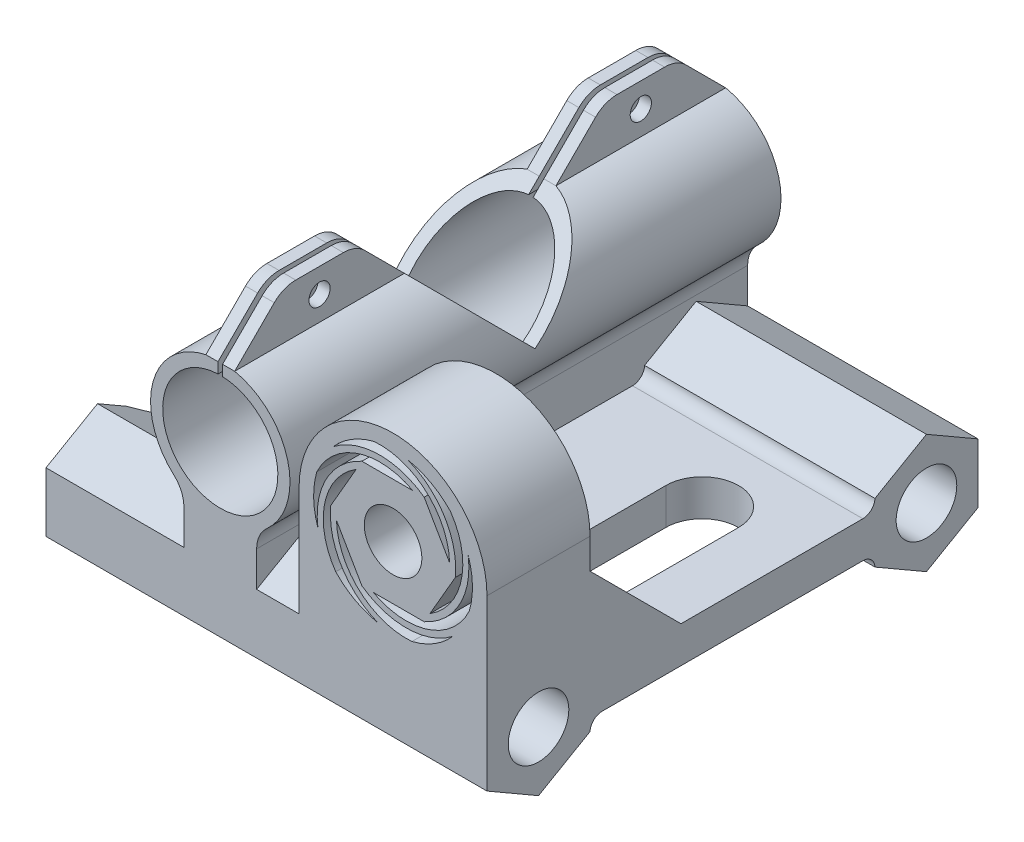
SolidWorks part; units mm, degrees
ref_plane "Front Plane" through (0, 0, 0) normal (0, 0, 1) x (1, 0, 0)
ref_plane "Top Plane" through (0, 0, 0) normal (0, 1, 0) x (1, 0, 0)
ref_plane "Right Plane" through (0, 0, 0) normal (1, 0, 0) x (0, 0, -1)
sketch "Sketch2" plane through (0, 0, 0) normal (1, 0, 0) x (0, 0, -1)
  line L0 (-5.6113, 0) -> (58.3887, 0) construction
  line L1 (2.8887, 3) -> (49.8887, 3)
  line L2 (66.8887, 4.9075) -> (58.3887, 9.815)
  line L3 (58.3887, 9.815) -> (49.8887, 4.9075)
  line L4 (49.8887, 4.9075) -> (49.8887, 3)
  line L5 (49.8887, -4.9075) -> (58.3887, -9.815)
  line L6 (58.3887, -9.815) -> (66.8887, -4.9075)
  line L7 (66.8887, -4.9075) -> (66.8887, 4.9075)
  line L8 (2.8887, 4.9075) -> (-5.6113, 9.815)
  line L9 (-5.6113, 9.815) -> (-14.1113, 4.9075)
  line L10 (-14.1113, 4.9075) -> (-14.1113, -4.9075)
  line L11 (-14.1113, -4.9075) -> (-5.6113, -9.815)
  line L12 (-5.6113, -9.815) -> (2.8887, -4.9075)
  line L13 (2.8887, -4.9075) -> (2.8887, -3)
  line L14 (2.8887, -3) -> (49.8887, -3)
  line L15 (49.8887, -3) -> (49.8887, -4.9075)
  line L16 (2.8887, 3) -> (2.8887, 4.9075)
  circle A2 centre (58.3887, 0) radius 8.5 construction
  circle A3 centre (-5.6113, 0) radius 8.5 construction
  dimension "D2" = 17
  dimension "D3" = 47
  dimension "D4" = 6
  dimension "D5" = 3
extrude "Boss-Extrude1" add sketch "Sketch2" along normal blind 72.75
sketch "Sketch3" plane through (0, 3, 0) normal (0, 1, 0) x (1, 0, 0)
  line L0 (0, 49.8887) -> (47, 2.8887) construction
  line L1 (72.75, 2.8887) -> (0, 2.8887) construction
  line L2 (0, 2.8887) -> (47, 49.8887) construction
  line L3 (72.75, 49.8887) -> (0, 49.8887) construction
  line L4 (72.75, 2.8887) -> (0, 2.8887) construction
  line L5 (1.75, 48.1387) -> (1.75, 2.8887)
  line L6 (39, 41.8887) -> (8, 41.8887) construction
  line L7 (39, 41.8887) -> (39, 10.8887) construction
  line L8 (39, 10.8887) -> (8, 10.8887) construction
  line L9 (8, 41.8887) -> (8, 10.8887) construction
  line L10 (1.75, 48.1387) -> (45.25, 48.1387) construction
  line L11 (45.25, 48.1387) -> (45.25, 4.6387) construction
  line L12 (45.25, 4.6387) -> (1.75, 4.6387) construction
  line L13 (1.75, 2.8887) -> (0, -0.8613)
  line L14 (0, 2.8887) -> (0, -5.6113) construction
  line L16 (1.75, 48.1387) -> (1.75, 49.8887)
  line L18 (1.75, 49.8887) -> (0, 51.6387)
  line L20 (0, 58.3887) -> (0, 49.8887) construction
  line L21 (0, 51.6387) -> (0, -0.8613)
  dimension "D1" = 45
  dimension "D2" = 45
  dimension "D3" = 31
  dimension "D6" = 43.5
extrude "Cut-Extrude1" cut sketch "Sketch3" against normal blind 28 and the other way blind 30
fillet "Fillet3" radius 2 4 edges at (37.25, -3, -2.8887) (37.25, -3, -49.8887) (37.25, 3, -49.8887) (37.25, 3, -2.8887)
sketch "Sketch4" plane through (0, 0, -66.8887) normal (0, 0, -1) x (-1, 0, 0)
  line L0 (-28.75, 3) -> (-28.75, 23) construction
  line L1 (-72.75, 3) -> (-1.75, 3) construction
  line L3 (-34.75, 3) -> (-34.75, 13.1893)
  line L4 (-22.75, 3) -> (-22.75, 13.1893)
  line L5 (-22.75, 3) -> (-34.75, 3)
  line L6 (-26.375, 34.2521) -> (-26.375, 42.2521)
  line L7 (-26.375, 42.2521) -> (-28.375, 42.2521)
  line L8 (-28.375, 42.2521) -> (-28.375, 32.4926)
  line L9 (-31.125, 34.2521) -> (-31.125, 42.2521)
  line L10 (-31.125, 42.2521) -> (-29.125, 42.2521)
  line L11 (-29.125, 42.2521) -> (-29.125, 32.4926)
  line L12 (-1.75, 4.9075) -> (-1.75, -4.9075) construction
  arc A0 (-29.125, 32.4926) -> (-28.375, 32.4926) centre (-28.75, 23) ccw
  arc A1 (-22.75, 13.1893) -> (-26.375, 34.2521) centre (-28.75, 23) ccw
  arc A3 (-31.125, 34.2521) -> (-34.75, 13.1893) centre (-28.75, 23) ccw
  dimension "D1" = 2
  dimension "D2" = 2
  dimension "D3" = 0.75
  dimension "D10" = 8
  dimension "D6" = 19
  dimension "D7" = 23
  dimension "D4" = 12
  dimension "D5" = 6
  dimension "D8" = 20
  dimension "D9" = 0.375
  dimension "D11" = 27
extrude "Boss-Extrude2" add sketch "Sketch4" against normal up to surface (81 mm away) up to face at (36.375, 0, 14.1113)
fillet "Fillet4" radius 5 2 edges at (22.75, 13.1893, -26.3887) (34.75, 13.1893, -26.3887)
sketch "Sketch5" plane through (0, 0, 14.1113) normal (0, 0, -1) x (-1, 0, 0)
  line L0 (-28.75, 23) -> (-110, 23) construction
  line L1 (-72.75, 23) -> (-72.75, 4.9075)
  line L2 (-72.75, 4.9075) -> (-34.75, 4.9075) construction
  line L3 (-72.75, 4.9075) -> (-41.75, 4.9075)
  line L4 (-41.75, 4.9075) -> (-41.75, 23)
  circle A0 centre (-57.25, 23) radius 4.75
  arc A1 (-41.75, 23) -> (-72.75, 23) centre (-57.25, 23) ccw
  arc A2 (-29.125, 32.4926) -> (-28.375, 32.4926) centre (-28.75, 23) ccw construction
  dimension "D1" = 9.5
  dimension "D3" = 31
  dimension "D4" = 0
  dimension "D5" = 28.5
  dimension "D2" = 28.5
extrude "Boss-Extrude7" add sketch "Sketch5" along normal up to vertex (17 mm away) up to point (72.75, 4.9075, -2.8887)
sketch "Sketch6" plane through (0, 0, -2.8887) normal (0, 0, -1) x (-1, 0, 0)
  line L0 (-41.75, 9.815) -> (-34.75, 9.815) construction
  line L1 (-49.7444, 23) -> (-53.4972, 29.5)
  line L2 (-53.4972, 29.5) -> (-61.0028, 29.5)
  line L3 (-61.0028, 29.5) -> (-64.7556, 23)
  line L4 (-64.7556, 23) -> (-61.0028, 16.5)
  line L5 (-61.0028, 16.5) -> (-53.4972, 16.5)
  line L6 (-53.4972, 16.5) -> (-49.7444, 23)
  circle A0 centre (-57.25, 23) radius 6.5 construction
  dimension "D1" = 13
extrude "Cut-Extrude2" cut sketch "Sketch6" against normal blind 7.5
sketch "Sketch7" plane through (0, 0, 0) normal (-1, 0, 0) x (0, 0, 1)
  line L0 (14.1113, 42.2521) -> (-66.8887, 42.2521) construction
  line L1 (-66.8887, 34.2521) -> (-38.8887, 34.2521) construction
  line L2 (-66.8887, 34.2521) -> (-66.8887, 14.4284) construction
  line L3 (-66.8887, 14.4284) -> (-38.8887, 14.4284) construction
  line L4 (-38.8887, 34.2521) -> (-38.8887, 14.4284) construction
  line L6 (14.1113, 14.4284) -> (-13.8887, 14.4284) construction
  line L7 (14.1113, 14.4284) -> (14.1113, 34.2521) construction
  line L8 (14.1113, 34.2521) -> (-13.8887, 34.2521) construction
  line L9 (-13.8887, 14.4284) -> (-13.8887, 34.2521) construction
  line L10 (14.1113, 38.2521) -> (-67.3887, 38.2521) construction
  line L11 (14.1113, 14.4284) -> (14.1113, 34.2521) construction
  line L12 (-38.8887, 42.2521) -> (-66.8887, 42.2521) construction
  line L13 (-52.8887, 34.2521) -> (-52.8887, 42.2521) construction
  line L15 (0.1113, 34.2521) -> (0.1113, 42.2521) construction
  line L16 (-38.8887, 34.2521) -> (-26.3887, 21.7521)
  line L17 (-13.8887, 34.2521) -> (-26.3887, 21.7521)
  line L18 (-13.8887, 34.2521) -> (-13.8887, 42.2521)
  line L19 (-38.8887, 34.2521) -> (-38.8887, 42.2521)
  line L20 (-38.8887, 42.2521) -> (-13.8887, 42.2521)
  line L21 (-66.8887, 14.4284) -> (14.1113, 14.4284) construction
  line L22 (-13.8887, 42.2521) -> (14.1113, 42.2521) construction
  line L25 (14.1113, 42.2521) -> (14.1113, 34.2521) construction
  line L26 (14.1113, 34.2521) -> (-66.8887, 34.2521) construction
  circle A0 centre (0.1113, 38.2521) radius 1.75
  circle A1 centre (-52.8887, 38.2521) radius 1.75
  dimension "D3" = 3.5
  dimension "D1" = 28
  dimension "D2" = 28
  dimension "D4" = 45
  dimension "D5" = 45
extrude "Cut-Extrude3" cut sketch "Sketch7" against normal up to surface (41.75 mm away) up to face at (41.75, 13.126, 5.6113)
chamfer "Chamfer1" distance 8 angle 45 8 edges at (27.375, 42.2521, -66.8887) (30.125, 42.2521, -66.8887) (30.125, 42.2521, -38.8887) (27.375, 42.2521, -38.8887) (30.125, 42.2521, 14.1113) (27.375, 42.2521, 14.1113) (27.375, 42.2521, -13.8887) (30.125, 42.2521, -13.8887)
fillet "Fillet5" radius 5 8 edges at (27.375, 42.2521, 6.1113) (30.125, 42.2521, 6.1113) (30.125, 42.2521, -5.8887) (27.375, 42.2521, -5.8887) (27.375, 42.2521, -46.8887) (30.125, 42.2521, -46.8887) (30.125, 42.2521, -58.8887) (27.375, 42.2521, -58.8887)
sketch "Sketch9" plane through (72.75, 0, 0) normal (1, 0, 0) x (0, 0, -1)
  line L0 (-9.8613, 7.3612) -> (-1.3613, -7.3612) construction
  line L1 (-5.6113, 9.815) -> (-14.1113, 4.9075) construction
  line L2 (-5.6113, -9.815) -> (2.8887, -4.9075) construction
  line L3 (54.1387, -7.3612) -> (62.6387, 7.3612) construction
  line L4 (49.8887, -4.9075) -> (58.3887, -9.815) construction
  circle A0 centre (58.3887, 0) radius 5
  circle A1 centre (-5.6113, 0) radius 5
  dimension "D1" = 10
extrude "Cut-Extrude5" cut sketch "Sketch9" against normal up to surface (50 mm away) up to face at (22.75, 6.5862, -26.3887)
sketch "Sketch14" plane through (0, 3, 0) normal (0, 1, 0) x (1, 0, 0)
  line L0 (57.75, 64.8887) -> (57.75, -14.1113) construction
  line L3 (72.75, 47.8909) -> (72.75, 4.8866) construction
  line L4 (57.75, 36.3887) -> (57.75, 14.3887) construction
  line L5 (63.75, 36.3887) -> (63.75, 14.3887)
  line L6 (51.75, 36.3887) -> (51.75, 14.3887)
  line L8 (41.75, -14.1113) -> (34.75, -14.1113) construction
  arc A0 (63.75, 36.3887) -> (51.75, 36.3887) centre (57.75, 36.3887) ccw
  arc A1 (51.75, 14.3887) -> (63.75, 14.3887) centre (57.75, 14.3887) ccw
  point P10 (57.75, 25.3887)
  dimension "D2" = 6
  dimension "D1" = 15
  dimension "D3" = 22
extrude "Cut-Extrude8" cut sketch "Sketch14" against normal blind 10
sketch "Sketch18" plane through (72.75, 0, 0) normal (1, 0, 0) x (0, 0, -1)
  line L0 (2.8941, 18) -> (2.8941, 3)
  line L1 (2.8941, 3) -> (17.8941, 3)
  line L2 (47.8909, 3) -> (4.8866, 3) construction
  line L3 (17.8941, 3) -> (2.8941, 18)
  dimension "D1" = 15
extrude "Boss-Extrude10" add sketch "Sketch18" against normal blind 3.5
sketch "Sketch19" plane through (41.75, 0, 0) normal (-1, 0, 0) x (0, 0, 1)
  line L0 (-2.8941, 18) -> (-17.8941, 3)
  line L1 (-17.8941, 3) -> (-2.8887, 3)
  line L2 (-2.8887, 4.9075) -> (-2.8887, -4.9075) construction
  line L3 (-2.8887, 3) -> (-2.8941, 18)
extrude "Boss-Extrude11" add sketch "Sketch19" against normal blind 3.5
sketch "Sketch20" plane through (0, 0, -2.8887) normal (0, 0, -1) x (-1, 0, 0)
  line L0 (-51.1697, 30.2686) -> (-46.9732, 23)
  line L1 (-49.7444, 23) -> (-53.4972, 29.5) construction
  line L2 (-46.9732, 23) -> (-52.1116, 31.9) construction
  line L3 (-52.1116, 31.9) -> (-62.3884, 31.9) construction
  line L4 (-62.3884, 31.9) -> (-67.5268, 23) construction
  line L5 (-67.5268, 23) -> (-62.3884, 14.1) construction
  line L6 (-62.3884, 14.1) -> (-52.1116, 14.1) construction
  line L7 (-52.1116, 14.1) -> (-46.9732, 23) construction
  line L8 (-53.4972, 29.5) -> (-61.0028, 29.5) construction
  line L9 (-47.9151, 21.3686) -> (-52.1116, 14.1)
  line L10 (-53.9954, 14.1) -> (-62.3884, 14.1)
  line L11 (-63.3303, 15.7314) -> (-67.5268, 23)
  line L12 (-66.5849, 24.6314) -> (-62.3884, 31.9)
  line L13 (-60.5046, 31.9) -> (-52.1116, 31.9)
  circle A0 centre (-57.25, 23) radius 8.9 construction
  arc A1 (-52.1116, 31.9) -> (-46.9708, 13.3654) centre (-57.2357, 20.4985) cw construction
  arc A2 (-44.8586, 18.75) -> (-44.6714, 26.6589) centre (-57.25, 23) ccw construction
  arc A3 (-41.75, 23) -> (-72.75, 23) centre (-57.25, 23) ccw construction
  arc A4 (-52.1116, 31.9) -> (-44.8586, 18.75) centre (-57.2357, 20.4985) cw
  arc A5 (-51.1697, 30.2686) -> (-47.792, 13.936) centre (-57.2357, 20.4985) cw
  arc A6 (-52.5215, 30.9879) -> (-47.792, 13.936) centre (-57.2357, 20.4985) cw construction
  arc A7 (-46.9732, 23) -> (-54.7349, 10.1437) centre (-59.4092, 21.7369) cw
  arc A8 (-47.9151, 21.3686) -> (-60.3706, 10.2771) centre (-59.4092, 21.7369) cw
  arc A9 (-52.1116, 14.1) -> (-67.1263, 14.3937) centre (-59.4235, 24.2383) cw
  arc A10 (-53.9954, 14.1) -> (-69.8286, 19.3411) centre (-59.4235, 24.2383) cw
  arc A11 (-62.3884, 14.1) -> (-69.6414, 27.25) centre (-57.2643, 25.5015) cw
  arc A12 (-63.3303, 15.7314) -> (-66.708, 32.064) centre (-57.2643, 25.5015) cw
  arc A13 (-67.5268, 23) -> (-59.7651, 35.8563) centre (-55.0908, 24.2631) cw
  arc A14 (-66.5849, 24.6314) -> (-54.1294, 35.7229) centre (-55.0908, 24.2631) cw
  arc A15 (-62.3884, 31.9) -> (-47.3737, 31.6063) centre (-55.0765, 21.7617) cw
  arc A16 (-60.5046, 31.9) -> (-44.6714, 26.6589) centre (-55.0765, 21.7617) cw
  arc A17 (-44.8586, 18.75) -> (-44.6714, 26.6589) centre (-57.25, 23) ccw
  arc A18 (-47.3737, 31.6063) -> (-54.1294, 35.7229) centre (-57.25, 23) ccw construction
  arc A19 (-47.3737, 31.6063) -> (-54.1294, 35.7229) centre (-57.25, 23) ccw
  arc A20 (-59.7651, 35.8563) -> (-66.708, 32.064) centre (-57.25, 23) ccw construction
  arc A21 (-59.7651, 35.8563) -> (-66.708, 32.064) centre (-57.25, 23) ccw
  arc A22 (-69.6414, 27.25) -> (-69.8286, 19.3411) centre (-57.25, 23) ccw construction
  arc A23 (-69.6414, 27.25) -> (-69.8286, 19.3411) centre (-57.25, 23) ccw
  arc A24 (-67.1263, 14.3937) -> (-60.3706, 10.2771) centre (-57.25, 23) ccw construction
  arc A25 (-67.1263, 14.3937) -> (-60.3706, 10.2771) centre (-57.25, 23) ccw
  arc A26 (-54.7349, 10.1437) -> (-47.792, 13.936) centre (-57.25, 23) ccw construction
  arc A27 (-54.7349, 10.1437) -> (-47.792, 13.936) centre (-57.25, 23) ccw
  point P55 (-57.25, 23)
  dimension "D1" = 2.4
  dimension "D5" = 4.25
  dimension "D4" = 12.5
  dimension "D2" = 2.4
  dimension "D3" = 1
extrude "Cut-Extrude9" cut sketch "Sketch20" against normal up to surface (17 mm away) up to face at (31.8889, 17.1213, 14.1113)
sketch "Sketch21" plane through (0, 0, -66.8887) normal (0, 0, -1) x (-1, 0, 0)
  line L1 (-41.6022, 43.1015) -> (8.7694, 43.1015)
  line L2 (-41.6022, 43.1015) -> (-41.6022, -11.7506)
  line L3 (-41.6022, -11.7506) -> (8.7694, -11.7506)
  line L4 (8.7694, 43.1015) -> (8.7694, -11.7506)
extrude "Cut-Extrude10" [suppressed] cut sketch "Sketch21" against normal blind 120
sketch "Sketch23" plane through (72.75, 0, 0) normal (1, 0, 0) x (0, 0, -1)
  line L1 (2.8887, 23) -> (75.5188, 23)
  line L2 (2.8887, 23) -> (2.8887, -21.0311)
  line L3 (2.8887, -21.0311) -> (75.5188, -21.0311)
  line L4 (75.5188, 23) -> (75.5188, -21.0311)
extrude "Cut-Extrude11" [suppressed] cut sketch "Sketch23" against normal blind 120
